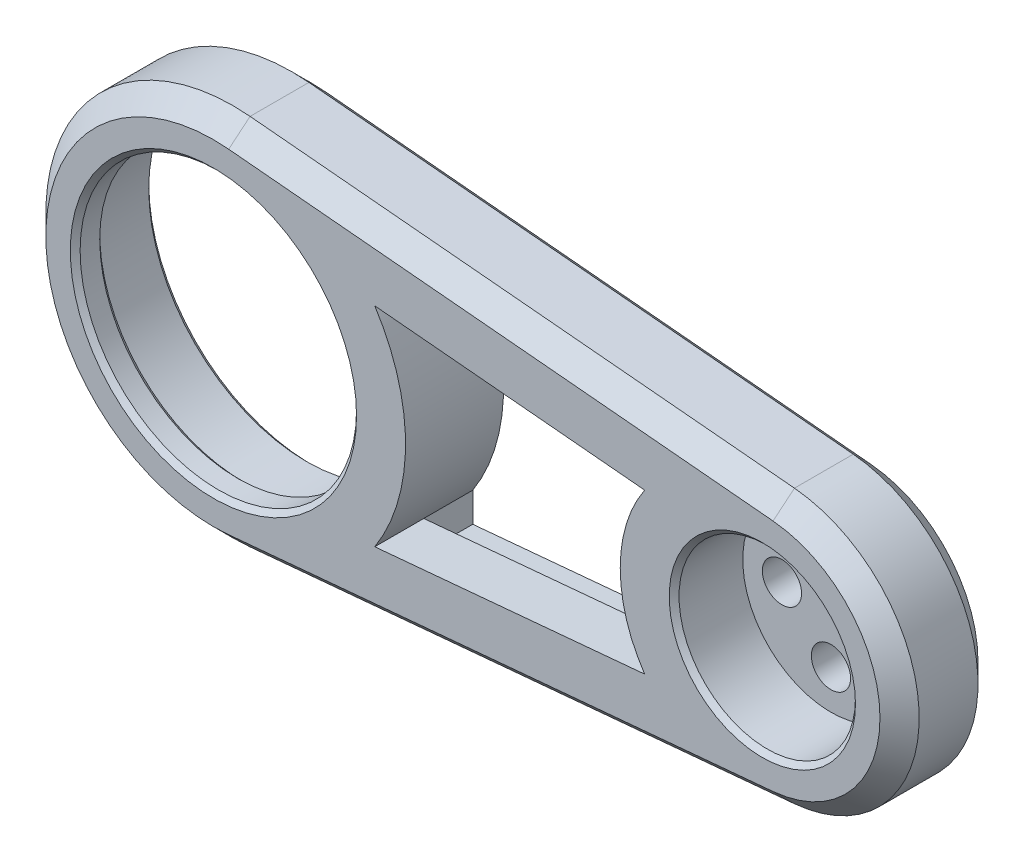
SolidWorks part; units mm, degrees
material "PEI"
ref_plane "前视基准面" through (0, 0, 0) normal (0, 0, 1) x (1, 0, 0)
ref_plane "上视基准面" through (0, 0, 0) normal (0, 1, 0) x (1, 0, 0)
ref_plane "右视基准面" through (0, 0, 0) normal (1, 0, 0) x (0, 0, -1)
other "Configuration Table"
sketch "草图2" plane through (0, 0, 0) normal (0, 0, 1) x (1, 0, 0)
  line L0 (0, 0) -> (56, 0) construction
  line L1 (1.7395, 19.0206) -> (57.275, 13.9418)
  line L2 (1.7395, -19.0206) -> (57.275, -13.9418)
  circle A0 centre (56, 0) radius 9
  circle A1 centre (56, 0) radius 14
  circle A2 centre (0, 0) radius 16.1
  circle A3 centre (0, 0) radius 19.1
  dimension "D1" = 18
  dimension "D2" = 28
  dimension "D4" = 32.2
  dimension "D3" = 56
  dimension "D5" = 3
extrude "凸台-拉伸1" add sketch "草图2" against normal blind 7 contours A2 A3 | A3 L0 A1 L1 | L0 A3 L2 A1 | A1 A0 region at (13.7083, -12.5119, 0) region at (29.9747, 9.296, 0) region at (29.9747, -9.296, 0) region at (46.829, 10.048, 0)
sketch "草图3" plane through (0, 0, -7) normal (0, 0, -1) x (-1, 0, 0)
  line L2 (-57.275, -13.9418) -> (-1.7395, -19.0206)
  line L3 (-1.7395, 19.0206) -> (-57.275, 13.9418)
  line L4 (-57.275, -13.9418) -> (-1.7395, -19.0206)
  line L5 (-1.7395, 19.0206) -> (-57.275, 13.9418)
  circle A0 centre (-56, 0) radius 9 construction
  circle A1 centre (-56, 0) radius 9
  arc A2 (-1.7395, -19.0206) -> (-1.7395, 19.0206) centre (0, 0) ccw
  arc A3 (-57.275, 13.9418) -> (-57.275, -13.9418) centre (-56, 0) ccw
  arc A4 (-1.7395, -19.0206) -> (-1.7395, 19.0206) centre (0, 0) ccw
  arc A5 (-57.275, 13.9418) -> (-57.275, -13.9418) centre (-56, 0) ccw
  circle A6 centre (0, 0) radius 16.1 construction
  circle A7 centre (0, 0) radius 16.1
  line M5 (-57.275, -13.9418) -> (-1.7395, -19.0206)
  arc M6 (-1.7395, -19.0206) -> (-1.7395, 19.0206) centre (0, 0) ccw
  line M7 (-1.7395, 19.0206) -> (-57.275, 13.9418)
  arc M8 (-57.275, 13.9418) -> (-57.275, -13.9418) centre (-56, 0) ccw
  circle M9 centre (0, 0) radius 16.1
  circle M10 centre (-56, 0) radius 9
  dimension "D1" = 0
extrude "凸台-拉伸2" add sketch "草图3" along normal blind 3 contours M10 | M8 M5 M6 M7 M9 M10 region at (29.651, 0, -7) region at (56, 0, -7)
sketch "草图4" plane through (0, 0, 0) normal (0, 0, 1) x (1, 0, 0)
  circle A0 centre (0, 0) radius 16.1 construction
  circle A1 centre (0, 0) radius 16.1
  circle A2 centre (0, 0) radius 14.1
  dimension "D1" = 2
extrude "凸台-拉伸3" add sketch "草图4" against normal blind 3
chamfer "倒角1" distance 0.5 angle 45 4 edges at (65, 0, 0) (-16.1, 0, -10) (14.1, 0, -3) (14.1, 0, 0)
chamfer "倒角2" distance 2 angle 45 8 edges at (29.5072, -16.4812, -10) (-19.1, 0, -10) (70, 0, -10) (29.5072, 16.4812, -10) (29.5072, -16.4812, 0) (-19.1, 0, 0) (70, 0, 0) (29.5072, 16.4812, 0)
sketch "草图5" plane through (0, 0, -10) normal (0, 0, -1) x (-1, 0, 0)
  line L0 (-85.5329, 0) -> (49.23, 0) construction
  line L1 (-56, 18.9424) -> (-56, -22.3961) construction
  circle A0 centre (-56, 0) radius 5 construction
  circle A1 centre (-56, 0) radius 9
  circle A2 centre (-56, 0) radius 9
  circle A3 centre (-56, 5) radius 2
  circle A4 centre (-51, 0) radius 2
  circle A5 centre (-56, -5) radius 2
  circle A6 centre (-61, 0) radius 2
  dimension "D2" = 10
  dimension "D3" = 4
  dimension "D1" = 0
  dimension "D4" = 4
extrude "切除-拉伸1" cut sketch "草图5" against normal up to surface (3 mm away) contours A3 | A6 | A5 | A4 region at (56, 5, -10) region at (51, 0, -10) region at (56, -5, -10) region at (61, 0, -10) up to face at (65, 0, -7)
sketch "草图6" plane through (0, 0, 0) normal (0, 0, 1) x (1, 0, 0)
  line L0 (56.6375, 6.9709) -> (1.102, 12.0497)
  line L1 (1.102, -12.0497) -> (56.6375, -6.9709)
  line L2 (1.5573, -17.0289) -> (57.0929, -11.9501)
  line L3 (57.0929, 11.9501) -> (1.5573, 17.0289)
  line L4 (1.5573, -17.0289) -> (57.0929, -11.9501)
  line L5 (57.0929, 11.9501) -> (1.5573, 17.0289)
  circle A0 centre (0, 0) radius 14.6 construction
  circle A1 centre (0, 0) radius 14.6
  arc A2 (1.5573, 17.0289) -> (1.5573, -17.0289) centre (0, 0) ccw
  arc A3 (57.0929, -11.9501) -> (57.0929, 11.9501) centre (56, 0) ccw
  arc A4 (1.5573, 17.0289) -> (1.5573, -17.0289) centre (0, 0) ccw
  arc A5 (57.0929, -11.9501) -> (57.0929, 11.9501) centre (56, 0) ccw
  circle A6 centre (56, 0) radius 9.5 construction
  circle A7 centre (56, 0) radius 9.5
  arc A9 (1.102, 12.0497) -> (1.102, -12.0497) centre (0, 0) ccw
  arc A10 (56.6375, -6.9709) -> (56.6375, 6.9709) centre (56, 0) ccw
  circle A12 centre (0, 0) radius 19.6
  circle A13 centre (56, 0) radius 14.5
  dimension "D1" = 0
  dimension "D2" = 5
  dimension "D3" = 5
extrude "切除-拉伸2" cut sketch "草图6" against normal up to surface (10 mm away) contours A13 L0 A12 L1 region at (29.9949, 0, 0) up to face at (54, 5, -10)
sketch "草图7" plane through (0, 0, -10) normal (0, 0, -1) x (-1, 0, 0)
  line L0 (-16.457, -10.6455) -> (-43.9918, -8.1274) construction
  line L1 (-43.9918, 8.1274) -> (-16.457, 10.6455) construction
  line L2 (-16.457, -10.6455) -> (-43.9918, -8.1274)
  line L3 (-43.9918, 8.1274) -> (-16.457, 10.6455)
  line L4 (-43.9918, 11.1399) -> (-16.457, 13.658)
  line L5 (-43.9918, -11.1399) -> (-16.457, -13.658)
  line L6 (-43.9918, -11.1399) -> (-43.9918, -8.1274)
  line L7 (-16.457, -13.658) -> (-16.457, -10.6455)
  line L8 (-16.457, 13.658) -> (-16.457, 10.6455)
  line L9 (-43.9918, 11.1399) -> (-43.9918, 8.1274)
  line M5 (-43.9918, 8.1274) -> (-16.457, 10.6455)
  line M7 (-16.457, -10.6455) -> (-43.9918, -8.1274)
  dimension "D1" = 3
  dimension "D2" = 3
extrude "切除-拉伸3" cut sketch "草图7" against normal blind 5 contours L4 L9 L8 M5 | L5 L7 L6 M7 region at (30.2244, -10.8927, -10) region at (30.2244, 10.8927, -10)
equation "\"D3@草图2\"= \"从动杆_后_长度\""
equation "\"从动杆_后_长度\"= 56"
